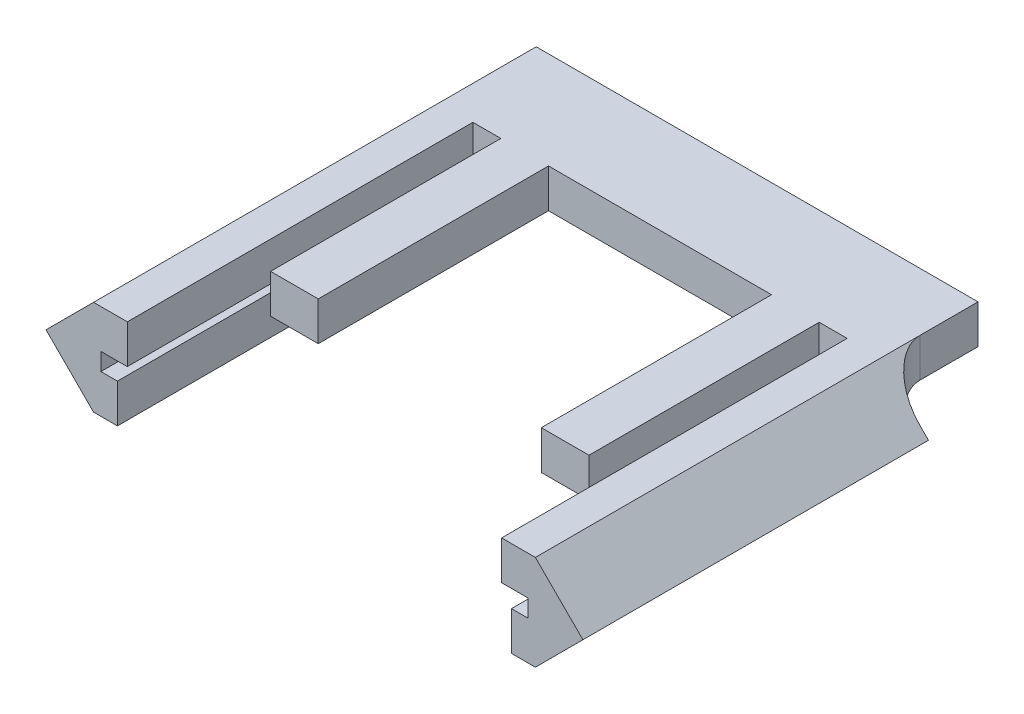
SolidWorks part; units mm, degrees
ref_plane "Front Plane" through (0, 0, 0) normal (0, 0, 1) x (1, 0, 0)
ref_plane "Top Plane" through (0, 0, 0) normal (0, 1, 0) x (1, 0, 0)
ref_plane "Right Plane" through (0, 0, 0) normal (1, 0, 0) x (0, 0, -1)
sketch "Sketch1" plane through (0, 0, 0) normal (0, 0, 1) x (1, 0, 0)
  line L0 (0.8255, 1.143) -> (0, 1.143)
  line L1 (0, 0) -> (0.8255, 0) construction
  line L2 (0, 0) -> (0, 1.143) construction
  line L3 (0, 1.143) -> (0.8255, 1.143) construction
  line L4 (0.8255, 0) -> (0.8255, 1.143) construction
  line L5 (0.4127, 1.143) -> (0.4128, 0) construction
  line L6 (0, 0.5715) -> (0.8255, 0.5715) construction
  line L7 (0.8255, 0) -> (0, 0)
  line L8 (0, 0) -> (-0.5715, 0.5715) construction
  line L9 (-0.5715, 0.5715) -> (0, 1.143) construction
  line L10 (25.9715, 0) -> (26.797, 0)
  line L11 (0.8255, 1.143) -> (25.9715, 1.143)
  line L12 (0.8255, 1.143) -> (0.8255, 0) construction
  line L13 (0.8255, 0) -> (25.9715, 0)
  line L14 (25.9715, 1.143) -> (25.9715, 0) construction
  line L15 (13.3985, 0) -> (13.3985, 1.143) construction
  line L16 (0.8255, 0.5715) -> (25.9715, 0.5715) construction
  line L17 (26.797, 0) -> (27.3685, 0.5715) construction
  line L18 (25.9715, 1.143) -> (26.797, 1.143)
  line L19 (27.3685, 0.5715) -> (26.797, 1.143) construction
  line L20 (-4.1636, 0.5715) -> (-1.0521, 3.683)
  line L21 (0.8255, 3.683) -> (-1.0521, 3.683)
  line L22 (0.8255, 3.683) -> (25.9715, 3.683)
  line L23 (25.9715, 3.683) -> (27.8491, 3.683)
  line L24 (30.9606, 0.5715) -> (27.8491, 3.683)
  line L25 (27.8491, -2.54) -> (30.9606, 0.5715)
  line L26 (25.9715, -2.54) -> (27.8491, -2.54)
  line L27 (0.8255, -2.54) -> (25.9715, -2.54)
  line L28 (0.8255, -2.54) -> (-1.0521, -2.54)
  line L29 (-1.0521, -2.54) -> (-4.1636, 0.5715)
  line L30 (0, 1.143) -> (-0.5715, 1.143)
  line L31 (-0.5715, 1.143) -> (-0.5715, 0)
  line L32 (-0.5715, 0) -> (0, 0)
  line L33 (26.797, 1.143) -> (27.3685, 1.143)
  line L34 (27.3685, 1.143) -> (27.3685, 0)
  line L35 (27.3685, 0) -> (26.797, 0)
  point P287 (13.3985, 0.5715)
  point P500 (0.4127, 0.5715)
  dimension "D1" = 1.143
  dimension "D2" = 0.8255
  dimension "D3" = 45
  dimension "D4" = 25.146
  dimension "D5" = 2.54
extrude "Boss-Extrude1" add sketch "Sketch1" along normal blind 22.606
sketch "Sketch2" plane through (0, 0, 22.606) normal (0, 0, 1) x (1, 0, 0)
  line L5 (13.3985, 0) -> (13.3985, -2.54) construction
  line L6 (-0.5715, 0) -> (27.3685, 0) construction
  line L7 (-1.0521, -2.54) -> (27.8491, -2.54) construction
  line L9 (0.508, 0) -> (26.289, 0)
  line L10 (0.508, 0) -> (0.508, -2.54)
  line L11 (0.508, -2.54) -> (26.289, -2.54)
  line L12 (26.289, 0) -> (26.289, -2.54)
  line L13 (13.3985, -2.54) -> (13.3985, 0) construction
  line L14 (0.508, -1.27) -> (26.289, -1.27) construction
  point P218 (13.3985, -1.27)
  dimension "D1" = 0.508
extrude "Cut-Extrude1" cut sketch "Sketch2" against normal blind 22.606
sketch "Sketch5" plane through (0, 0, 0) normal (0, 0, -1) x (-1, 0, 0)
  line L12 (-30.9606, 0.5715) -> (-27.3685, 0.5715)
  line L13 (-27.3685, 0.5715) -> (-27.3685, 1.143)
  line L14 (-27.3685, 1.143) -> (0.5715, 1.143)
  line L15 (0.5715, 1.143) -> (0.5715, 0.5715)
  line L16 (0.5715, 1.143) -> (0.5715, 0) construction
  line L17 (0.5715, 0.5715) -> (4.1636, 0.5715)
  line L18 (4.1636, 0.5715) -> (1.0521, 3.683)
  line L19 (1.0521, 3.683) -> (-27.8491, 3.683)
  line L20 (-27.8491, 3.683) -> (-30.9606, 0.5715)
extrude "Boss-Extrude2" add sketch "Sketch5" along normal blind 6.35
sketch "Sketch3" plane through (0, 3.683, 0) normal (0, 1, 0) x (1, 0, 0)
  line L0 (13.3985, 0) -> (13.3985, -22.606) construction
  line L1 (27.8491, 0) -> (-1.0521, 0) construction
  line L2 (27.8491, -22.606) -> (-1.0521, -22.606) construction
  line L3 (6.1023, -15.0622) -> (2.9845, -15.0622)
  line L4 (1.1557, 0) -> (25.6413, 0) construction
  line L5 (1.1557, 0) -> (1.1557, -22.606) construction
  line L6 (1.1557, -22.606) -> (25.6413, -22.606) construction
  line L7 (25.6413, 0) -> (25.6413, -22.606) construction
  line L8 (13.3985, -22.606) -> (13.3985, 0) construction
  line L9 (1.1557, -11.303) -> (25.6413, -11.303) construction
  line L10 (6.1023, 0) -> (20.6947, 0) construction
  line L11 (6.1023, 0) -> (6.1023, -15.0622)
  line L12 (6.1023, -15.0622) -> (20.6947, -15.0622) construction
  line L13 (20.6947, 0) -> (20.6947, -15.0622)
  line L14 (13.3985, -15.0622) -> (13.3985, 0) construction
  line L15 (6.1023, -7.5311) -> (20.6947, -7.5311) construction
  line L16 (2.9845, 0) -> (23.8125, 0) construction
  line L17 (2.9845, 0) -> (2.9845, -22.606) construction
  line L18 (2.9845, -22.606) -> (23.8125, -22.606) construction
  line L19 (23.8125, 0) -> (23.8125, -22.606) construction
  line L20 (13.3985, -22.606) -> (13.3985, 0) construction
  line L21 (2.9845, -11.303) -> (23.8125, -11.303) construction
  line L22 (2.9845, -15.0622) -> (2.9845, 0)
  line L23 (2.9845, 0) -> (1.1557, 0)
  line L24 (1.1557, 0) -> (1.1557, -22.606)
  line L25 (1.1557, -22.606) -> (25.6413, -22.606)
  line L26 (25.6413, -22.606) -> (25.6413, 0)
  line L27 (25.6413, 0) -> (23.8125, 0)
  line L28 (23.8125, 0) -> (23.8125, -15.0622)
  line L29 (23.8125, -15.0622) -> (20.6947, -15.0622)
  line L32 (6.1023, 0) -> (20.6947, 0)
  point P250 (13.3985, -11.303)
  point P383 (13.3985, -7.5311)
  point P386 (13.3985, -11.303)
  dimension "D1" = 24.4856
  dimension "D2" = 14.5923
  dimension "D3" = 15.0622
  dimension "D4" = 20.828
extrude "Cut-Extrude4" cut sketch "Sketch3" against normal up to vertex (2.54 mm away) up to point (27.3685, 1.143, 22.606)
sketch "Sketch6" plane through (0, 0, -6.35) normal (0, 0, -1) x (-1, 0, 0)
  line L2 (-27.8491, 3.683) -> (-30.9606, 0.5715)
  line L3 (-30.9606, 0.5715) -> (-27.3685, 0.5715)
  line L4 (-27.3685, 0.5715) -> (-27.3685, 1.143)
  line L5 (-27.3685, 1.143) -> (-27.8491, 1.143)
  line L6 (-27.8491, 1.143) -> (-27.8491, 3.683)
  line L8 (-13.3985, 3.683) -> (-13.3985, 1.143) construction
  line L9 (-0.8255, 3.683) -> (-25.9715, 3.683) construction
  line L11 (1.0521, 1.143) -> (1.0521, 3.683)
  line L12 (0.5715, 1.143) -> (1.0521, 1.143)
  line L13 (0.5715, 0.5715) -> (0.5715, 1.143)
  line L14 (4.1636, 0.5715) -> (0.5715, 0.5715)
  line L15 (1.0521, 3.683) -> (4.1636, 0.5715)
extrude "Cut-Extrude5" cut sketch "Sketch6" against normal up to surface (6.35 mm away) up to face at (27.6875, -0.6562, 0)
fillet "Fillet1" radius 2.54 4 edges at (-0.8118, 1.143, 0) (-1.0521, 2.413, 0) (27.6088, 1.143, 0) (27.8491, 2.413, 0)
